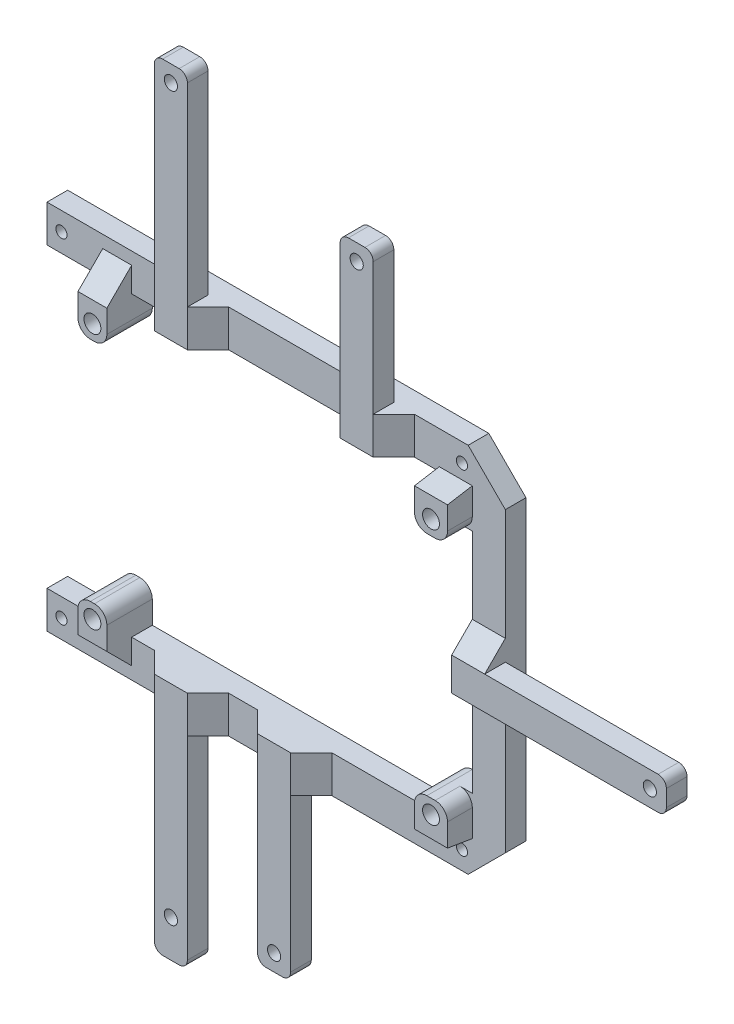
SolidWorks part; units mm, degrees
ref_plane "Front Plane" through (0, 0, 0) normal (0, 0, 1) x (1, 0, 0)
ref_plane "Top Plane" through (0, 0, 0) normal (0, 1, 0) x (1, 0, 0)
ref_plane "Right Plane" through (0, 0, 0) normal (1, 0, 0) x (0, 0, -1)
sketch "Sketch1" plane through (0, 0, 0) normal (0, 0, 1) x (1, 0, 0)
  line L0 (-68, 36) -> (-61, 36) construction
  line L1 (-61, 36) -> (-61, 43) construction
  line L2 (-61, -36) -> (-61, -43) construction
  line L3 (-68, -36) -> (-61, -36) construction
  line L4 (61, -43) -> (61, -36) construction
  line L5 (61, -36) -> (68, -36) construction
  line L6 (61, 43) -> (61, 36) construction
  line L7 (61, 36) -> (68, 36) construction
  line L8 (68, -36) -> (68, 36) construction
  line L9 (-35, 43) -> (-61, 43) construction
  line L10 (61, 43) -> (49, 43) construction
  line L11 (42, 43) -> (2, 43) construction
  line L12 (-5, 43) -> (-28, 43) construction
  line L13 (-61, -43) -> (-35, -43) construction
  line L14 (49, -43) -> (61, -43) construction
  line L15 (2, -43) -> (42, -43) construction
  line L16 (-28, -43) -> (-5, -43) construction
  line L17 (-67, 45) -> (-76, 36) construction
  line L18 (-76, 36) -> (-76, -36) construction
  line L19 (-76, -36) -> (-67, -45) construction
  line L20 (-67, -45) -> (67, -45) construction
  line L21 (67, -45) -> (70, -42) construction
  line L22 (70, -42) -> (76, -36) construction
  line L23 (76, -36) -> (76, 36) construction
  line L24 (70, 42) -> (67, 45) construction
  line L25 (76, 36) -> (70, 42) construction
  line L26 (67, 45) -> (-67, 45) construction
  line L27 (-68, 36) -> (-61, 36)
  line L28 (-61, 36) -> (-61, 43)
  line L29 (-61, -36) -> (-61, -43)
  line L30 (-68, -36) -> (-61, -36)
  line L31 (61, -43) -> (61, -36)
  line L32 (61, -36) -> (68, -36)
  line L33 (61, 43) -> (61, 36)
  line L34 (61, 36) -> (68, 36)
  line L35 (68, -36) -> (68, 36)
  line L36 (-35, 43) -> (-61, 43)
  line L37 (61, 43) -> (49, 43)
  line L38 (42, 43) -> (2, 43)
  line L39 (-5, 43) -> (-28, 43)
  line L40 (-61, -43) -> (-35, -43)
  line L41 (49, -43) -> (61, -43)
  line L42 (2, -43) -> (42, -43)
  line L43 (-28, -43) -> (-5, -43)
  line L44 (-67, 45) -> (-76, 36)
  line L45 (-76, 36) -> (-76, -36)
  line L46 (-76, -36) -> (-67, -45)
  line L47 (-67, -45) -> (67, -45)
  line L48 (67, -45) -> (70, -42)
  line L49 (70, -42) -> (76, -36)
  line L50 (76, -36) -> (76, 36)
  line L51 (70, 42) -> (67, 45)
  line L52 (76, 36) -> (70, 42)
  line L53 (67, 45) -> (-67, 45)
  circle A2 centre (-72, 30) radius 2.05 construction
  circle A3 centre (-65.5, 13.5) radius 2.05 construction
  circle A4 centre (-65.5, -13.5) radius 2.05 construction
  circle A5 centre (-72, -30) radius 2.05 construction
  circle A6 centre (-65.5, -40.5) radius 2.05 construction
  circle A7 centre (-31.5, -40.5) radius 2.05 construction
  circle A8 centre (-1.5, -40.5) radius 2.05 construction
  circle A9 centre (45.5, -40.5) radius 2.05 construction
  circle A10 centre (65.5, -40.5) radius 2.05 construction
  circle A11 centre (65.5, 40.5) radius 2.05 construction
  circle A12 centre (45.5, 40.5) radius 2.05 construction
  circle A13 centre (-1.5, 40.5) radius 2.05 construction
  circle A14 centre (-31.5, 40.5) radius 2.05 construction
  circle A15 centre (-65.5, 40.5) radius 2.05 construction
  circle A18 centre (-72, 30) radius 2.05
  circle A19 centre (-65.5, 13.5) radius 2.05
  circle A20 centre (-65.5, -13.5) radius 2.05
  circle A21 centre (-72, -30) radius 2.05
  circle A22 centre (-65.5, -40.5) radius 2.05
  circle A23 centre (-31.5, -40.5) radius 2.05
  circle A24 centre (-1.5, -40.5) radius 2.05
  circle A25 centre (45.5, -40.5) radius 2.05
  circle A26 centre (65.5, -40.5) radius 2.05
  circle A27 centre (65.5, 40.5) radius 2.05
  circle A28 centre (45.5, 40.5) radius 2.05
  circle A29 centre (-1.5, 40.5) radius 2.05
  circle A30 centre (-31.5, 40.5) radius 2.05
  circle A31 centre (-65.5, 40.5) radius 2.05
sketch "Sketch2" plane through (0, 0, 0) normal (0, 0, 1) x (1, 0, 0)
  line L0 (-35, -45) -> (67, -45)
  line L1 (-67, -45) -> (67, -45) construction
  line L2 (67, -45) -> (76, -36)
  line L3 (76, -36) -> (76, 36)
  line L4 (76, -36) -> (76, 36) construction
  line L6 (-35, -36) -> (-35, -45)
  line L7 (76, 0) -> (68, 0) construction
  line L8 (68, -36) -> (68, 36) construction
  line L9 (68, 36) -> (68, -36)
  line L10 (68, -36) -> (-35, -36)
  line L11 (76, 0) -> (-44.0125, 0) construction
  line L12 (68, 36) -> (-35, 36)
  line L13 (-35, 36) -> (-35, 45)
  line L14 (67, 45) -> (76, 36)
  line L15 (-35, 45) -> (67, 45)
  circle A0 centre (-31.5, -40.5) radius 1.35
  circle A1 centre (-31.5, 40.5) radius 1.35
  circle A2 centre (-31.5, -40.5) radius 2.05 construction
  circle A5 centre (-31.5, -40.5) radius 2.05 construction
  circle A6 centre (65.5, -40.5) radius 2.05 construction
  circle A7 centre (65.5, -40.5) radius 2.05 construction
  circle A8 centre (65.5, 40.5) radius 2.05 construction
  circle A9 centre (-31.5, 40.5) radius 2.05 construction
  circle A10 centre (65.5, 40.5) radius 1.35
  circle A11 centre (65.5, -40.5) radius 1.35
  dimension "D3" = 2.7
  dimension "D1" = 3.5
  dimension "D2" = 36
extrude "Boss-Extrude2" add sketch "Sketch2" along normal blind 5
sketch "Sketch3" plane through (0, 0, 5) normal (0, 0, 1) x (1, 0, 0)
  line L0 (68, -36) -> (-35, -36) construction
  line L1 (-21.5, -36) -> (-14.5, -36)
  line L2 (-21.5, -36) -> (-21.5, -27.5)
  line L3 (-21.5, -27.5) -> (-14.5, -27.5)
  line L4 (-14.5, -36) -> (-14.5, -27.5)
  line L5 (68, 36) -> (68, -36) construction
  line L6 (68, -36) -> (60, -36)
  line L7 (68, -36) -> (68, -27.5)
  line L8 (68, -27.5) -> (60, -27.5)
  line L9 (60, -36) -> (60, -27.5)
  line L10 (-35, -45) -> (67, -45) construction
  circle A0 centre (-18, -31) radius 2.05
  circle A1 centre (64, -31) radius 2.05
  point P12 (-18, -27.5)
  point P13 (64, -27.5)
  dimension "D7" = 4.1
  dimension "7" = 7
  dimension "D2" = 82
  dimension "8" = 8
  dimension "D4" = 14
  dimension "D6" = 3.5
extrude "Boss-Extrude3" add sketch "Sketch3" against normal up to surface (5 mm away) and the other way blind 6 up to face at (28.2, 0, 0)
fillet "Fillet1" radius 3 4 edges at (68, -27.5, 8) (60, -27.5, 5.5) (-14.5, -27.5, 5.5) (-21.5, -27.5, 5.5)
chamfer "Chamfer1" distance 6 angle 45 1 edges at (-18, -36, 5)
chamfer "Chamfer2" distance 6 distance2 1 1 edges at (64, -36, 5) first distance on face at (64, -36, 8)
ref_plane "Plane2" through (0, 0, 0) normal (0, -1, 0) x (-1, 0, 0)
mirror "Mirror5" about plane through (0, 0, 0) normal (0, -1, 0) of "Boss-Extrude3"
fillet "Fillet2" radius 3 4 edges at (60, 27.5, 5.5) (68, 27.5, 8) (-21.5, 27.5, 5.5) (-14.5, 27.5, 5.5)
chamfer "Chamfer4" distance 6 angle 45 1 edges at (-18, 36, 5)
chamfer "Chamfer5" distance 6 distance2 1 1 edges at (64, 36, 5) first distance on face at (64, 36, 8)
sketch "Sketch4" plane through (0, 0, 5) normal (0, 0, 1) x (1, 0, 0)
  line L0 (60, -36) -> (-14.5, -36) construction
  line L1 (-5, -36) -> (3, -36)
  line L2 (-5, -36) -> (-5, -45)
  line L3 (-5, -45) -> (3, -45)
  line L4 (3, -36) -> (3, -45)
  line L5 (-35, -45) -> (67, -45) construction
  line L6 (-35, -36) -> (-35, -45) construction
  line L7 (28, -36) -> (36, -36)
  line L8 (28, -36) -> (28, -45)
  line L9 (28, -45) -> (36, -45)
  line L10 (36, -36) -> (36, -45)
  dimension "D1" = 8
  dimension "D2" = 30
  dimension "D3" = 25
extrude "Boss-Extrude4" add sketch "Sketch4" along normal blind 8
sketch "Sketch5" plane through (0, -45, 0) normal (0, -1, 0) x (1, 0, 0)
  line L0 (-1, 13) -> (-1, 0) construction
  line L1 (-5, 13) -> (3, 13) construction
  line L2 (-35, 0) -> (67, 0) construction
  line L3 (32, 13) -> (32, 0) construction
  line L4 (28, 13) -> (36, 13) construction
  circle A0 centre (-1, 9.5) radius 2.05
  circle A1 centre (32, 9.5) radius 2.05
  dimension "D1" = 4.1
  dimension "D2" = 3.5
extrude "Cut-Extrude1" cut sketch "Sketch5" against normal up to surface (9 mm away) up to face at (-28.25, -36, 2.5)
mirror "Mirror6" about plane through (0, 0, 0) normal (0, -1, 0) of "Cut-Extrude1", "Boss-Extrude4"
sketch "Sketch6" plane through (0, 0, 5) normal (0, 0, 1) x (1, 0, 0)
  line L0 (76, -36) -> (76, 36) construction
  line L1 (76, -4) -> (68, -4)
  line L2 (76, -4) -> (76, 4)
  line L3 (76, 4) -> (68, 4)
  line L4 (68, -4) -> (68, 4)
  line L5 (68, 27.5) -> (68, -27.5) construction
  line L6 (28, -45) -> (36, -45) construction
  point P9 (76, 0)
  point P10 (76, 0)
extrude "Boss-Extrude5" add sketch "Sketch6" along normal up to surface (8 mm away) up to face at (32, -40.5, 13)
sketch "Sketch7" plane through (76, 0, 0) normal (1, 0, 0) x (0, 0, -1)
  line L0 (-11.55, -45) -> (-7.45, -45) construction
  line L1 (-11.55, -45) -> (-7.45, -45) construction
  line L2 (-13, -4) -> (-13, 4) construction
  line L3 (-7.45, -45) -> (-7.45, 0) construction
  circle A0 centre (-9.5, 0) radius 2.05
  point P7 (-13, 0)
  point P9 (-9.5, -45)
extrude "Cut-Extrude2" cut sketch "Sketch7" against normal up to surface (8 mm away) up to face at (68, 0, 5.75)
sketch "Sketch8" plane through (0, 0, 5) normal (0, 0, 1) x (1, 0, 0)
  line L0 (-5, -36) -> (-5, -45) construction
  line L1 (-5, -45) -> (3, -45) construction
  line L2 (3, -45) -> (3, -36) construction
  line L3 (3, -36) -> (-5, -36) construction
  line L4 (28, -36) -> (28, -45) construction
  line L5 (28, -45) -> (36, -45) construction
  line L6 (36, -45) -> (36, -36) construction
  line L7 (36, -36) -> (28, -36) construction
  line L8 (68, -4) -> (76, -4) construction
  line L9 (76, -4) -> (76, 4) construction
  line L10 (76, 4) -> (68, 4) construction
  line L11 (68, 4) -> (68, -4) construction
  line L12 (28, 45) -> (28, 36) construction
  line L13 (28, 36) -> (36, 36) construction
  line L14 (36, 36) -> (36, 45) construction
  line L15 (36, 45) -> (28, 45) construction
  line L16 (-5, 45) -> (-5, 36) construction
  line L17 (-5, 36) -> (3, 36) construction
  line L18 (3, 36) -> (3, 45) construction
  line L19 (3, 45) -> (-5, 45) construction
  line L20 (-5, -36) -> (-5, -45)
  line L21 (-5, -45) -> (3, -45)
  line L22 (3, -45) -> (3, -36)
  line L23 (3, -36) -> (-5, -36)
  line L24 (28, -36) -> (28, -45)
  line L25 (28, -45) -> (36, -45)
  line L26 (36, -45) -> (36, -36)
  line L27 (36, -36) -> (28, -36)
  line L28 (68, -4) -> (76, -4)
  line L29 (76, -4) -> (76, 4)
  line L30 (76, 4) -> (68, 4)
  line L31 (68, 4) -> (68, -4)
  line L32 (28, 45) -> (28, 36)
  line L33 (28, 36) -> (36, 36)
  line L34 (36, 36) -> (36, 45)
  line L35 (36, 45) -> (28, 45)
  line L36 (-5, 45) -> (-5, 36)
  line L37 (-5, 36) -> (3, 36)
  line L38 (3, 36) -> (3, 45)
  line L39 (3, 45) -> (-5, 45)
extrude "Cut-Extrude4" cut sketch "Sketch8" along normal up to surface (8 mm away) up to face at (-1, 40.5, 13)
sketch "Sketch9" plane through (0, 0, 5) normal (0, 0, 1) x (1, 0, 0)
  line L0 (60, -36) -> (-14.5, -36) construction
  line L1 (-4, -36) -> (4, -36)
  line L2 (-4, -36) -> (-4, -94)
  line L3 (-4, -94) -> (4, -94)
  line L4 (4, -36) -> (4, -94)
  line L5 (-35, -45) -> (67, -45) construction
  line L6 (-35, -36) -> (-35, -45) construction
  line L7 (-14.5, 36) -> (60, 36) construction
  line L8 (-4, 36) -> (4, 36)
  line L9 (-4, 36) -> (-4, 94)
  line L10 (-4, 94) -> (4, 94)
  line L11 (4, 36) -> (4, 94)
  line L12 (68, 27.5) -> (68, -27.5) construction
  line L13 (41, 36) -> (49, 36)
  line L14 (41, 36) -> (41, 79)
  line L15 (41, 79) -> (49, 79)
  line L16 (49, 36) -> (49, 79)
  line L17 (21, -36) -> (29, -36)
  line L18 (21, -36) -> (21, -84)
  line L19 (21, -84) -> (29, -84)
  line L20 (29, -36) -> (29, -84)
  line L21 (68, 4) -> (120, 4)
  line L22 (68, 4) -> (68, -4)
  line L23 (68, -4) -> (120, -4)
  line L24 (120, 4) -> (120, -4)
  line L25 (67, 45) -> (-35, 45) construction
  line L26 (76, -36) -> (76, 36) construction
  circle A0 centre (0, -90) radius 16.8341 construction
  circle A1 centre (0, 90) radius 13.9601 construction
  circle A2 centre (45, 75) radius 18.436 construction
  circle A3 centre (116, 0) radius 17.4807 construction
  circle A4 centre (25, -80) radius 15.3213 construction
  point P12 (0, -94)
  point P42 (0, 94)
  point P44 (45, 79)
  point P46 (120, 0)
  point P50 (25, -84)
  dimension "D10" = 30
  dimension "D11" = 35
  dimension "D12" = 40
  dimension "D13" = 45
  dimension "D14" = 25
  dimension "D1" = 8
  dimension "D2" = 4
  dimension "D3" = 31
  dimension "D4" = 45
  dimension "D5" = 4
  dimension "D6" = 4
  dimension "D7" = 4
  dimension "D8" = 4
  dimension "D9" = 45
extrude "Boss-Extrude6" add sketch "Sketch9" along normal blind 5
sketch "Sketch10" plane through (0, 0, 10) normal (0, 0, 1) x (1, 0, 0)
  line L0 (-4, -94) -> (4, -94) construction
  line L1 (4, -45) -> (21, -45) construction
  circle A0 centre (0, -85) radius 1.6
  circle A1 centre (0, 90) radius 1.6
  circle A2 centre (45, 75) radius 1.6
  circle A3 centre (116, 0) radius 1.6
  circle A4 centre (25, -80) radius 1.6
  point P5 (0, -94)
  dimension "D1" = 3.2
  dimension "D2" = 40
extrude "Cut-Extrude5" cut sketch "Sketch10" against normal through all
fillet "Fillet3" radius 2 10 edges at (-4, -94, 7.5) (4, -94, 7.5) (-4, 94, 7.5) (4, 94, 7.5) (41, 79, 7.5) (49, 79, 7.5) (120, 4, 7.5) (120, -4, 7.5) (29, -84, 7.5) (21, -84, 7.5)
sketch "Sketch11" plane through (0, 0, 10) normal (0, 0, 1) x (1, 0, 0)
  line L0 (0, -36) -> (0, -94) construction
  line L1 (4, -36) -> (-4, -36) construction
  line L2 (-2, -94) -> (2, -94) construction
chamfer "Chamfer6" distance 5 angle 45 10 edges at (21, -40.5, 5) (-4, -40.5, 5) (4, -40.5, 5) (72, 4, 5) (29, -40.5, 5) (72, -4, 5) (49, 40.5, 5) (41, 40.5, 5) (-4, 40.5, 5) (4, 40.5, 5)
